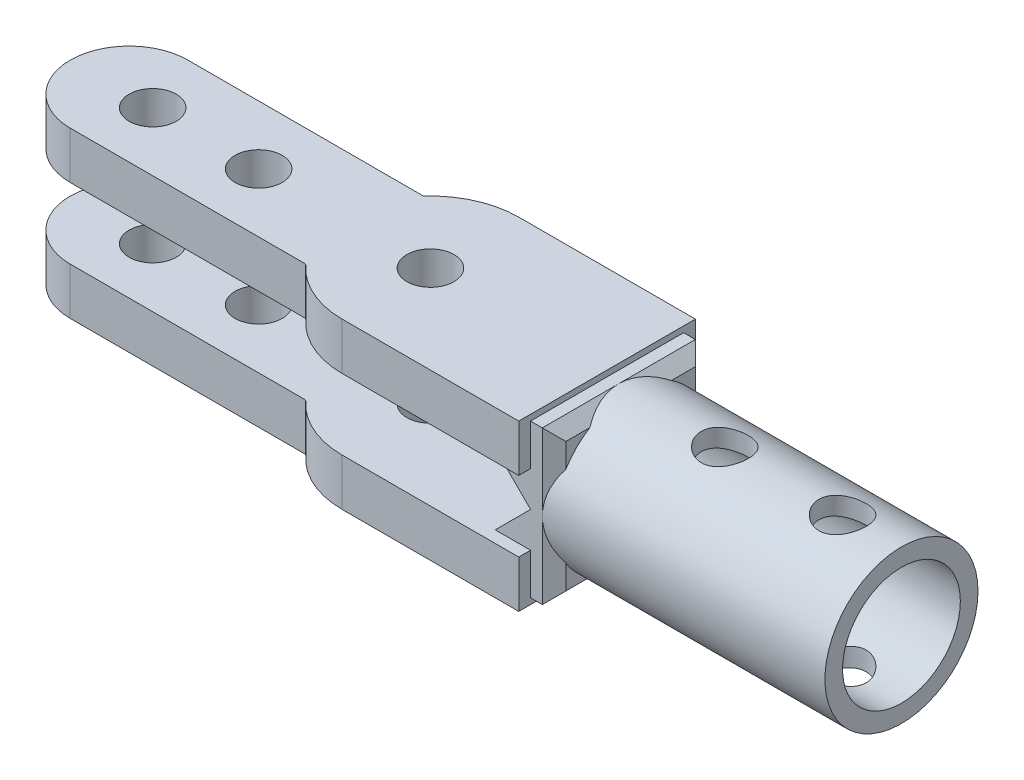
SolidWorks part; units mm, degrees
ref_plane "Front Plane" through (0, 0, 0) normal (0, 0, 1) x (1, 0, 0)
ref_plane "Top Plane" through (0, 0, 0) normal (0, 1, 0) x (1, 0, 0)
ref_plane "Right Plane" through (0, 0, 0) normal (1, 0, 0) x (0, 0, -1)
sketch "Sketch1" plane through (0, 0, 0) normal (1, 0, 0) x (0, 0, -1)
  circle A0 centre (0, 0) radius 5
  circle A1 centre (0, 0) radius 6.5
  dimension "D1" = 10
  dimension "D2" = 13
extrude "Boss-Extrude1" add sketch "Sketch1" along normal blind 23
sketch "Sketch2" plane through (0, 0, 0) normal (1, 0, 0) x (0, 0, -1)
  line L9 (6.5, -6.5) -> (-6.5, -6.5)
  line L10 (6.5, -6.5) -> (6.5, 6.5)
  line L11 (6.5, 6.5) -> (-6.5, 6.5)
  line L12 (-6.5, -6.5) -> (-6.5, 6.5)
  line L13 (6.5, -6.5) -> (-6.5, 6.5) construction
  line L14 (6.5, 6.5) -> (-6.5, -6.5) construction
  circle A0 centre (0, 0) radius 6.5 construction
  point P0 (0, 0)
extrude "Boss-Extrude2" add sketch "Sketch2" against normal blind 2
sketch "Sketch3" plane through (0, 0, 0) normal (0, 1, 0) x (1, 0, 0)
  line L1 (-2, -7.5) -> (-2, 7.5)
  line L11 (-17, -7.5) -> (-2, -7.5)
  line L13 (-17, 7.5) -> (-2, 7.5)
  line L14 (-42.5902, -5) -> (-22.5902, -5)
  line L15 (-42.5902, -5) -> (-42.5902, 5) construction
  line L16 (-42.5902, 5) -> (-22.5902, 5)
  line L17 (-22.5902, -5) -> (-22.5902, 5) construction
  line L18 (-42.5902, -5) -> (-22.5902, 5) construction
  line L19 (-42.5902, 5) -> (-22.5902, -5) construction
  arc A2 (-17, 7.5) -> (-22.5902, 5) centre (-17, 0) ccw
  circle A3 centre (-17, 0) radius 2
  arc A4 (-42.5902, 5) -> (-42.5902, -5) centre (-42.5902, 0) ccw
  arc A5 (-22.5902, -5) -> (-17, -7.5) centre (-17, 0) ccw
  circle A6 centre (-39.5902, 0) radius 2
  circle A7 centre (-29.5902, 0) radius 2
  point P0 (-32.5902, 0)
  point P2 (-9.5853, 0)
  point P19 (0, 0)
  point P20 (0, 0)
  dimension "D2" = 7.5
  dimension "D3" = 4
  dimension "D7" = 5
  dimension "D8" = 4
  dimension "D9" = 4
  dimension "D1" = 15
  dimension "D4" = 2
  dimension "D5" = 10
  dimension "D6" = 20
  dimension "D10" = 10
  dimension "D11" = 3
sketch "Sketch4" plane through (0, 0, 0) normal (0, 1, 0) x (1, 0, 0)
  line L1 (23, -6.5) -> (23, 6.5) construction
  circle A0 centre (8, 0) radius 2
  circle A1 centre (18, 0) radius 2
  dimension "D1" = 4
  dimension "D2" = 5
  dimension "D3" = 10
extrude "Cut-Extrude1" cut sketch "Sketch4" against normal through all both and the other way through all
ref_plane "Plane2" through (0, 7, 0) normal (0, 1, 0) x (1, 0, 0)
sketch "Sketch5" plane through (0, 7, 0) normal (0, 1, 0) x (1, 0, 0)
  line L0 (-2, 7.5) -> (-2, -7.5)
  line L3 (-2, -7.5) -> (-2, 7.5)
  line L7 (-22.5902, 5) -> (-42.5902, 5)
  line L12 (-17, -7.5) -> (-2, -7.5)
  line L13 (-2, 7.5) -> (-17, 7.5)
  line L15 (-17, -7.5) -> (-2, -7.5)
  line L16 (-2, 7.5) -> (-17, 7.5)
  line L17 (-22.5902, 5) -> (-42.5902, 5)
  line L18 (-2, -7.5) -> (-2, 7.5)
  line L19 (-42.5902, -5) -> (-22.5902, -5)
  line L20 (-42.5902, -5) -> (-22.5902, -5)
  circle A0 centre (-40.5902, 0) radius 2
  circle A1 centre (-17, 0) radius 2
  circle A2 centre (-17, 0) radius 2
  arc A3 (-17, 7.5) -> (-22.5902, 5) centre (-17, 0) ccw
  arc A4 (-17, 7.5) -> (-22.5902, 5) centre (-17, 0) ccw
  circle A5 centre (-31.5902, 0) radius 2
  arc A7 (-42.5902, 5) -> (-42.5902, -5) centre (-42.5902, 0) ccw
  arc A8 (-42.5902, 5) -> (-42.5902, -5) centre (-42.5902, 0) ccw
  arc A9 (-22.5902, -5) -> (-17, -7.5) centre (-17, 0) ccw
  arc A10 (-22.5902, -5) -> (-17, -7.5) centre (-17, 0) ccw
  dimension "D1" = 9
  dimension "D4" = 4
  dimension "D5" = 2
  dimension "D2" = 0
  dimension "D3" = 0
extrude "Boss-Extrude5" add sketch "Sketch5" against normal blind 4 contours L16 A4 L15 L0 A2 region at (-21.4575, 7, 0)
mirror "Mirror2" about plane through (0, 0, 0) normal (0, 1, 0) of "Boss-Extrude5"
chamfer "Chamfer2" distance 3 angle 45 2 edges at (-2, 3, 0) (-2, -3, 0)
sketch "Sketch6" plane through (0, 0, 0) normal (0, 1, 0) x (1, 0, 0)
  line L0 (-42.5902, -5) -> (-42.5902, -4)
  line L1 (-42.5902, 4) -> (-42.5902, 5)
  arc A0 (-42.5902, 5) -> (-42.5902, -5) centre (-42.5902, 0) ccw construction
  arc A1 (-42.5902, 5) -> (-42.5902, -5) centre (-42.5902, 0) ccw
  arc A2 (-42.5902, 4) -> (-42.5902, -4) centre (-42.5902, 0) ccw
  dimension "D1" = 1
extrude "Boss-Extrude6" [suppressed] add sketch "Sketch6" along normal mid plane 50
chamfer "Chamfer3" distance 1 angle 45 8 edges at (0, 3.25, -6.5) (0, -3.25, -6.5) (0, -6.5, -3.25) (0, -6.5, 3.25) (0, -3.25, 6.5) (0, 3.25, 6.5) (0, 6.5, 3.25) (0, 6.5, -3.25)
